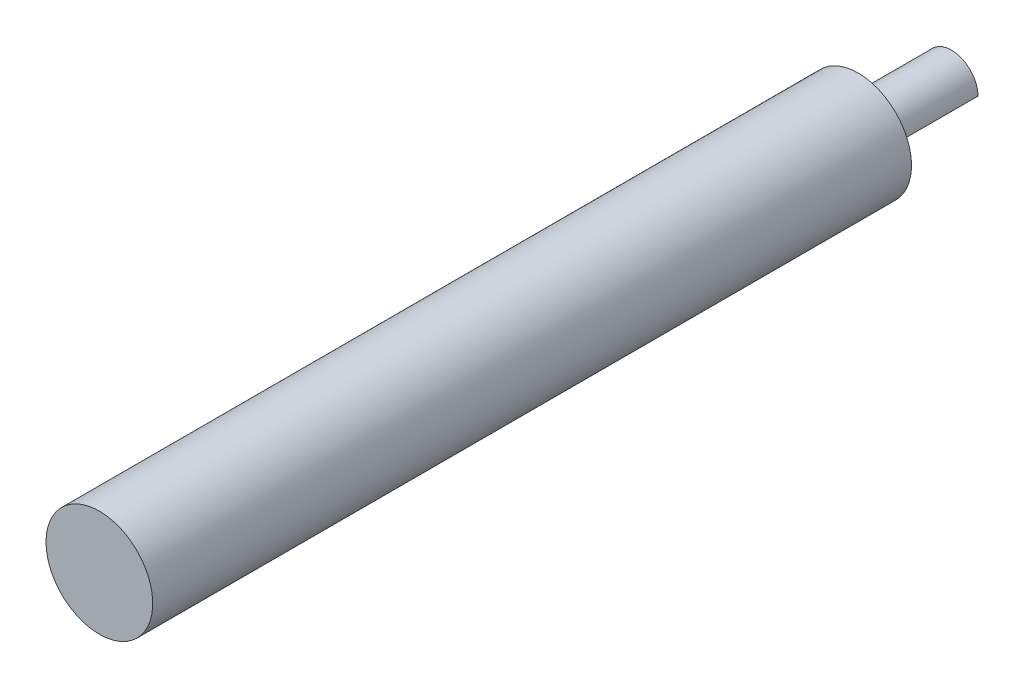
SolidWorks part; units mm, degrees
material "AISI 1020"
ref_plane "Front Plane" through (0, 0, 0) normal (0, 0, 1) x (1, 0, 0)
ref_plane "Top Plane" through (0, 0, 0) normal (0, 1, 0) x (1, 0, 0)
ref_plane "Right Plane" through (0, 0, 0) normal (1, 0, 0) x (0, 0, -1)
sketch "Sketch1" plane through (0, 0, 0) normal (0, 0, 1) x (1, 0, 0)
  circle A0 centre (0, 0) radius 3.1623
  dimension "D1" = 6.3246
extrude "Boss-Extrude1" add sketch "Sketch1" along normal blind 11.0998
sketch "Sketch2" plane through (0, 0, 0) normal (0, 0, -1) x (-1, 0, 0)
  line L0 (0.0012, -3.1623) -> (-3.1623, 0.0012)
  circle A0 centre (0, 0) radius 3.1623 construction
  dimension "D1" = 2.2352
extrude "Cut-Extrude1" cut sketch "Sketch2" against normal through all and the other way through all
sketch "Sketch3" plane through (0, 0, 11.0998) normal (0, 0, 1) x (1, 0, 0)
  circle A0 centre (0, 0) radius 6.35
  dimension "D1" = 12.7
extrude "Boss-Extrude2" add sketch "Sketch3" along normal blind 90.297
sketch "Sketch5" plane through (0, 0, 101.3968) normal (0, 0, 1) x (1, 0, 0)
  circle A0 centre (0, 0) radius 6.35
fillet "Fillet1" [suppressed] radius 1.27 type face fillet
